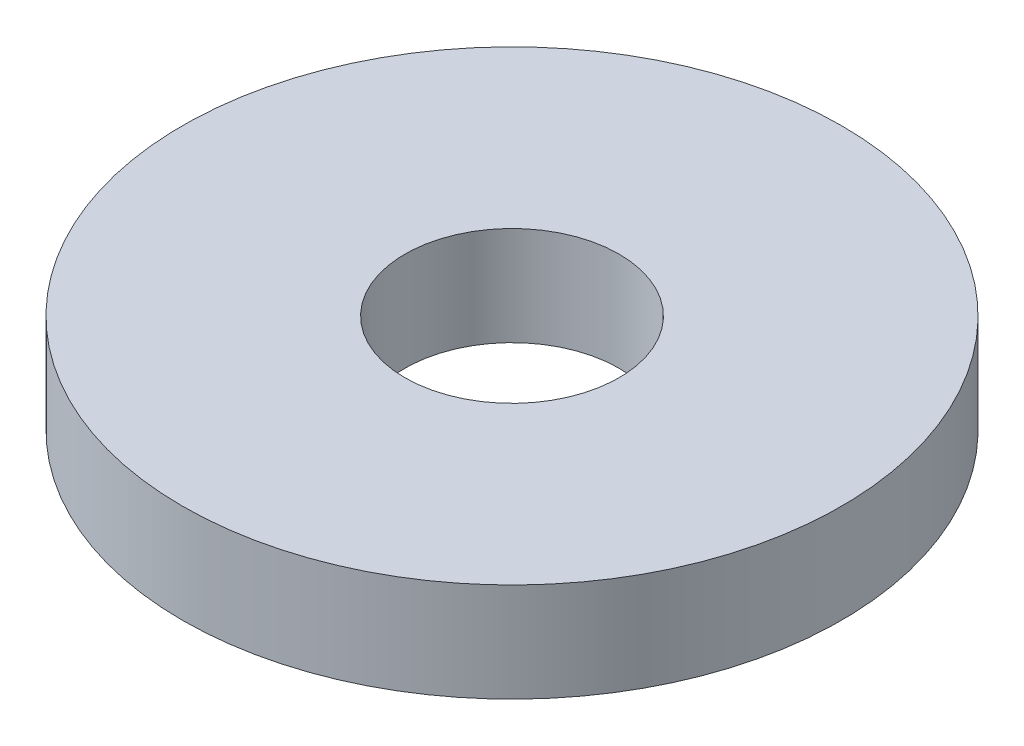
SolidWorks part; units mm, degrees
ref_plane "Plan de face" through (0, 0, 0) normal (0, 0, 1) x (1, 0, 0)
ref_plane "Plan de dessus" through (0, 0, 0) normal (0, 1, 0) x (1, 0, 0)
ref_plane "Plan de droite" through (0, 0, 0) normal (1, 0, 0) x (0, 0, -1)
sketch "Esquisse1" plane through (0, 0, 0) normal (0, 1, 0) x (1, 0, 0)
  circle A0 centre (0, 0) radius 3.25
  circle A1 centre (0, 0) radius 10
  dimension "D1" = 6.5
  dimension "D2" = 20
extrude "Boss.-Extru.1" add sketch "Esquisse1" along normal blind 3
